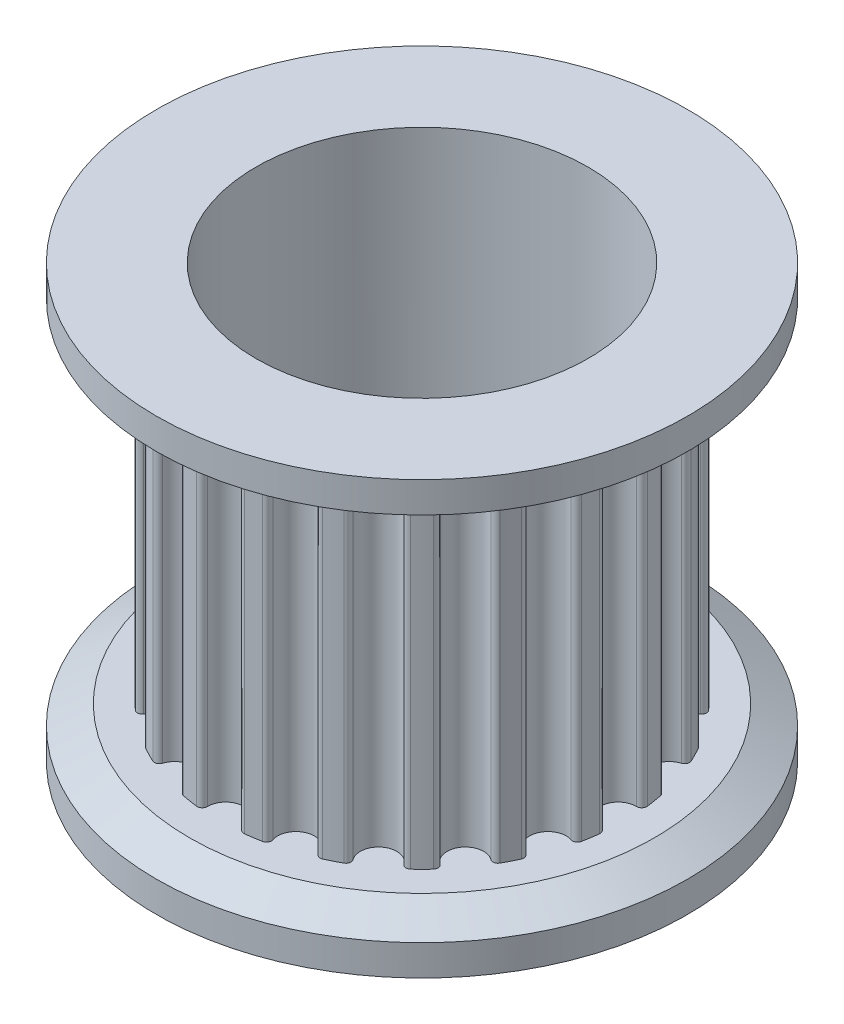
SolidWorks part; units mm, degrees
note: '?' marks a value the reader was unsure of.
material "1060 Сплав"
ref_plane "Спереди" through (0, 0, 0) normal (0, 0, 1) x (1, 0, 0)
ref_plane "Сверху" through (0, 0, 0) normal (0, 1, 0) x (1, 0, 0)
ref_plane "Справа" through (0, 0, 0) normal (1, 0, 0) x (0, 0, -1)
other "Configuration Table"
sketch "Эскиз1" plane through (0, 0, 0) normal (0, 1, 0) x (1, 0, 0)
  circle A0 centre (0, 0) radius 8
  circle A1 centre (0, 0) radius 5
  dimension "D1" = 16
  dimension "D2" = 10
extrude "Бобышка-Вытянуть1" add sketch "Эскиз1" along normal blind 7.45
sketch "Эскиз2" plane through (0, 7.45, 0) normal (0, 1, 0) x (1, 0, 0)
  arc A0 (-2.5575, 5.549) -> (-2.986, 5.3307) centre (0, 0) ccw
  circle A1 centre (0, 0) radius 5 construction
  circle A2 centre (0, 0) radius 5
  arc A3 (-0.55, 5.9169) -> (0.55, 5.9169) centre (0, 5.91) ccw
  arc A4 (1.3054, 5.7972) -> (2.3515, 5.4573) centre (1.8263, 5.6207) ccw
  arc A5 (3.0329, 5.1101) -> (3.9228, 4.4636) centre (3.4738, 4.7813) ccw
  arc A6 (4.4636, 3.9228) -> (5.1101, 3.0329) centre (4.7813, 3.4738) ccw
  arc A7 (5.4573, 2.3515) -> (5.7972, 1.3054) centre (5.6207, 1.8263) ccw
  arc A8 (5.9169, 0.55) -> (5.9169, -0.55) centre (5.91, 0) ccw
  arc A9 (5.7972, -1.3054) -> (5.4573, -2.3515) centre (5.6207, -1.8263) ccw
  arc A10 (5.1101, -3.0329) -> (4.4636, -3.9228) centre (4.7813, -3.4738) ccw
  arc A11 (3.9228, -4.4636) -> (3.0329, -5.1101) centre (3.4738, -4.7813) ccw
  arc A12 (2.3515, -5.4573) -> (1.3054, -5.7972) centre (1.8263, -5.6207) ccw
  arc A13 (0.55, -5.9169) -> (-0.55, -5.9169) centre (0, -5.91) ccw
  arc A14 (-1.3054, -5.7972) -> (-2.3515, -5.4573) centre (-1.8263, -5.6207) ccw
  arc A15 (-3.0329, -5.1101) -> (-3.9228, -4.4636) centre (-3.4738, -4.7813) ccw
  arc A16 (-4.4636, -3.9228) -> (-5.1101, -3.0329) centre (-4.7813, -3.4738) ccw
  arc A17 (-5.4573, -2.3515) -> (-5.7972, -1.3054) centre (-5.6207, -1.8263) ccw
  arc A18 (-5.9169, -0.55) -> (-5.9169, 0.55) centre (-5.91, 0) ccw
  arc A19 (-5.7972, 1.3054) -> (-5.4573, 2.3515) centre (-5.6207, 1.8263) ccw
  arc A20 (-5.1101, 3.0329) -> (-4.4636, 3.9228) centre (-4.7813, 3.4738) ccw
  arc A21 (-3.9228, 4.4636) -> (-3.0329, 5.1101) centre (-3.4738, 4.7813) ccw
  arc A22 (-2.3515, 5.4573) -> (-1.3054, 5.7972) centre (-1.8263, 5.6207) ccw
  arc A23 (-4.147, 4.4871) -> (-4.4871, 4.147) centre (0, 0) ccw
  arc A24 (-0.7176, 6.0677) -> (-1.1926, 5.9925) centre (0, 0) ccw
  arc A25 (1.1926, 5.9925) -> (0.7176, 6.0677) centre (0, 0) ccw
  arc A26 (2.986, 5.3307) -> (2.5575, 5.549) centre (0, 0) ccw
  arc A27 (4.4871, 4.147) -> (4.147, 4.4871) centre (0, 0) ccw
  arc A28 (5.549, 2.5575) -> (5.3307, 2.986) centre (0, 0) ccw
  arc A29 (6.0677, 0.7176) -> (5.9925, 1.1926) centre (0, 0) ccw
  arc A30 (-5.3307, 2.986) -> (-5.549, 2.5575) centre (0, 0) ccw
  arc A31 (-5.9925, 1.1926) -> (-6.0677, 0.7176) centre (0, 0) ccw
  arc A32 (-6.0677, -0.7176) -> (-5.9925, -1.1926) centre (0, 0) ccw
  arc A33 (-5.549, -2.5575) -> (-5.3307, -2.986) centre (0, 0) ccw
  arc A34 (-4.4871, -4.147) -> (-4.147, -4.4871) centre (0, 0) ccw
  arc A35 (-2.986, -5.3307) -> (-2.5575, -5.549) centre (0, 0) ccw
  arc A36 (5.9925, -1.1926) -> (6.0677, -0.7176) centre (0, 0) ccw
  arc A37 (5.3307, -2.986) -> (5.549, -2.5575) centre (0, 0) ccw
  arc A38 (4.147, -4.4871) -> (4.4871, -4.147) centre (0, 0) ccw
  arc A39 (2.5575, -5.549) -> (2.986, -5.3307) centre (0, 0) ccw
  arc A40 (0.7176, -6.0677) -> (1.1926, -5.9925) centre (0, 0) ccw
  arc A41 (-1.1926, -5.9925) -> (-0.7176, -6.0677) centre (0, 0) ccw
  arc A42 (5.9169, 0.55) -> (6.0677, 0.7176) centre (5.9188, 0.6999) ccw
  arc A43 (5.7972, 1.3054) -> (5.9925, 1.1926) centre (5.8454, 1.1633) cw
  arc A44 (5.4573, 2.3515) -> (5.549, 2.5575) centre (5.4128, 2.4947) ccw
  arc A45 (5.1101, 3.0329) -> (5.3307, 2.986) centre (5.1998, 2.9127) cw
  arc A46 (5.1101, -3.0329) -> (5.3307, -2.986) centre (5.1998, -2.9127) ccw
  arc A47 (5.4573, -2.3515) -> (5.549, -2.5575) centre (5.4128, -2.4947) cw
  arc A48 (5.7972, -1.3054) -> (5.9925, -1.1926) centre (5.8454, -1.1633) ccw
  arc A49 (5.9169, -0.55) -> (6.0677, -0.7176) centre (5.9188, -0.6999) cw
  arc A50 (3.9228, -4.4636) -> (4.147, -4.4871) centre (4.0452, -4.377) ccw
  arc A51 (4.4636, -3.9228) -> (4.4871, -4.147) centre (4.377, -4.0452) cw
  arc A52 (3.0329, -5.1101) -> (2.986, -5.3307) centre (2.9127, -5.1998) cw
  arc A53 (1.3054, -5.7972) -> (1.1926, -5.9925) centre (1.1633, -5.8454) cw
  arc A54 (0.55, -5.9169) -> (0.7176, -6.0677) centre (0.6999, -5.9188) ccw
  arc A55 (-0.55, -5.9169) -> (-0.7176, -6.0677) centre (-0.6999, -5.9188) cw
  arc A56 (-1.3054, -5.7972) -> (-1.1926, -5.9925) centre (-1.1633, -5.8454) ccw
  arc A57 (-2.3515, -5.4573) -> (-2.5575, -5.549) centre (-2.4947, -5.4128) cw
  arc A58 (-3.0329, -5.1101) -> (-2.986, -5.3307) centre (-2.9127, -5.1998) ccw
  arc A59 (-3.9228, -4.4636) -> (-4.147, -4.4871) centre (-4.0452, -4.377) cw
  arc A60 (-4.4636, -3.9228) -> (-4.4871, -4.147) centre (-4.377, -4.0452) ccw
  arc A61 (-5.9169, -0.55) -> (-6.0677, -0.7176) centre (-5.9188, -0.6999) ccw
  arc A62 (-5.7972, -1.3054) -> (-5.9925, -1.1926) centre (-5.8454, -1.1633) cw
  arc A63 (-5.4573, -2.3515) -> (-5.549, -2.5575) centre (-5.4128, -2.4947) ccw
  arc A64 (-5.1101, -3.0329) -> (-5.3307, -2.986) centre (-5.1998, -2.9127) cw
  arc A65 (-5.1101, 3.0329) -> (-5.3307, 2.986) centre (-5.1998, 2.9127) ccw
  arc A66 (-5.4573, 2.3515) -> (-5.549, 2.5575) centre (-5.4128, 2.4947) cw
  arc A67 (-5.7972, 1.3054) -> (-5.9925, 1.1926) centre (-5.8454, 1.1633) ccw
  arc A68 (-5.9169, 0.55) -> (-6.0677, 0.7176) centre (-5.9188, 0.6999) cw
  arc A69 (-4.4636, 3.9228) -> (-4.4871, 4.147) centre (-4.377, 4.0452) cw
  arc A70 (-3.9228, 4.4636) -> (-4.147, 4.4871) centre (-4.0452, 4.377) ccw
  arc A71 (-3.0329, 5.1101) -> (-2.986, 5.3307) centre (-2.9127, 5.1998) cw
  arc A72 (-2.3515, 5.4573) -> (-2.5575, 5.549) centre (-2.4947, 5.4128) ccw
  arc A73 (-1.3054, 5.7972) -> (-1.1926, 5.9925) centre (-1.1633, 5.8454) cw
  arc A74 (-0.55, 5.9169) -> (-0.7176, 6.0677) centre (-0.6999, 5.9188) ccw
  arc A75 (4.4636, 3.9228) -> (4.4871, 4.147) centre (4.377, 4.0452) ccw
  arc A76 (3.9228, 4.4636) -> (4.147, 4.4871) centre (4.0452, 4.377) cw
  arc A77 (0.55, 5.9169) -> (0.7176, 6.0677) centre (0.6999, 5.9188) cw
  arc A78 (1.3054, 5.7972) -> (1.1926, 5.9925) centre (1.1633, 5.8454) ccw
  arc A79 (3.0329, 5.1101) -> (2.986, 5.3307) centre (2.9127, 5.1998) ccw
  arc A80 (2.3515, 5.4573) -> (2.5575, 5.549) centre (2.4947, 5.4128) cw
  arc A81 (2.3515, -5.4573) -> (2.5575, -5.549) centre (2.4947, -5.4128) ccw
  point P69 (0, 0)
  point P135 (-0.5205, 6.0878)
  point P142 (0.5205, 6.0878)
  dimension "D1" = 12.22
  dimension "D2" = 1.1
  dimension "D3" = 0.75
  dimension "D5" = 0.15
  dimension "D6" = 0.15
  dimension "D4" = 20
extrude "Бобышка-Вытянуть2" add sketch "Эскиз2" along normal blind 10
sketch "Эскиз3" plane through (0, 17.45, 0) normal (0, 1, 0) x (1, 0, 0)
  circle A0 centre (0, 0) radius 5 construction
  circle A1 centre (0, 0) radius 5
  circle A2 centre (0, 0) radius 8 construction
  circle A3 centre (0, 0) radius 8
extrude "Бобышка-Вытянуть3" add sketch "Эскиз3" along normal blind 1.5
sketch "Минимальный радиус ремня" plane through (0, 7.45, 0) normal (0, 1, 0) x (1, 0, 0)
  circle A0 centre (0, 0) radius 5.36
  arc A2 (-2.986, -5.3307) -> (-2.5575, -5.549) centre (0, 0) ccw construction
  dimension "D1" = 0.75
  dimension "D2" = 10.72
chamfer "Фаска1" distance 1 angle 30 2 edges at (0, 17.45, 8) (0, 7.45, 8)
ref_axis "Ось1" through (0, 18.95, 0) along (0, -1, 0)?
sketch "草图1" plane through (0, 0, 0) normal (0, -1, 0) x (1, 0, 0)
  circle A1 centre (0, 0) radius 8
  circle A2 centre (0, 0) radius 8
  dimension "D1" = 0
extrude "切除-拉伸1" cut sketch "草图1" against normal blind 5.95
